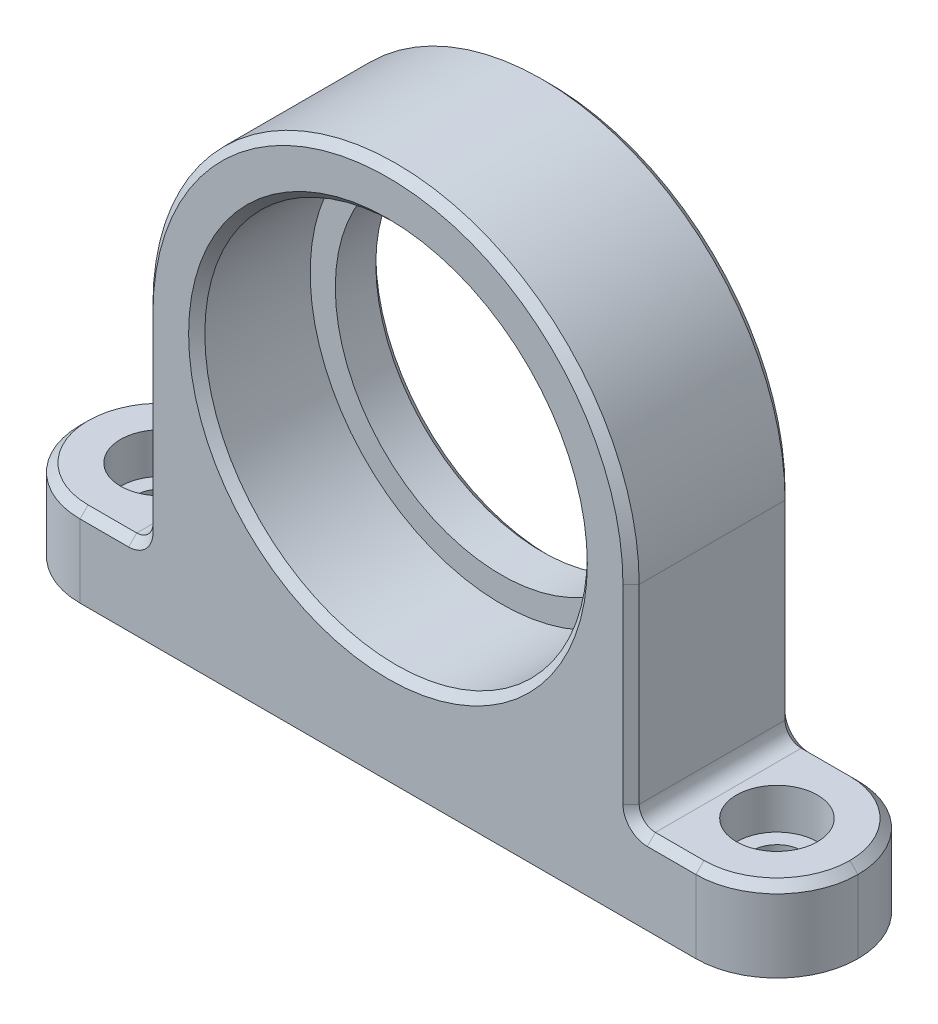
SolidWorks part; units mm, degrees
material "ABS"
ref_plane "前视基准面" through (0, 0, 0) normal (0, 0, 1) x (1, 0, 0)
ref_plane "上视基准面" through (0, 0, 0) normal (0, 1, 0) x (1, 0, 0)
ref_plane "右视基准面" through (0, 0, 0) normal (1, 0, 0) x (0, 0, -1)
sketch "草图1" plane through (0, 0, 0) normal (0, 1, 0) x (1, 0, 0)
  line L1 (-48, 10) -> (48, 10)
  line L2 (-48, 10) -> (-48, -10)
  line L3 (-48, -10) -> (48, -10)
  line L4 (48, 10) -> (48, -10)
  line L5 (-48, 10) -> (48, -10) construction
  line L6 (-48, -10) -> (48, 10) construction
  point P0 (0, 0)
extrude "凸台-拉伸1" add sketch "草图1" along normal blind 10 contours L2 L3 L4 L1
sketch "草图2" plane through (0, 10, 0) normal (0, 1, 0) x (1, 0, 0)
  line L0 (-48, 0) -> (-38, 0) construction
  line L1 (-48, 10) -> (-48, -10) construction
  line L2 (0, 0) -> (0, 10) construction
  line L3 (-48, 10) -> (48, 10) construction
  circle A0 centre (-38, 0) radius 5
  circle A1 centre (38, 0) radius 5
extrude "切除-拉伸1" cut sketch "草图2" against normal blind 5
fillet "圆角1" radius 10 4 edges at (48, 5, -10) (48, 5, 10) (-48, 5, 10) (-48, 5, -10)
sketch "草图3" plane through (0, 5, 0) normal (0, 1, 0) x (1, 0, 0)
  circle A0 centre (-38, 0) radius 3.1
  circle A1 centre (38, 0) radius 3.1
extrude "切除-拉伸2" cut sketch "草图3" against normal blind 5
chamfer "倒角1" distance 1 angle 45 2 edges at (38, 0, 3.1) (-38, 0, 3.1)
sketch "草图4" plane through (0, 10, 0) normal (0, 1, 0) x (1, 0, 0)
  line L0 (-38, 10) -> (38, 10) construction
  line L1 (-30, -10) -> (30, -10)
  line L2 (-30, -10) -> (-30, 10)
  line L3 (-30, 10) -> (30, 10)
  line L4 (30, -10) -> (30, 10)
  line L5 (-30, -10) -> (30, 10) construction
  line L6 (-30, 10) -> (30, -10) construction
  point P0 (0, 0)
extrude "凸台-拉伸2" add sketch "草图4" along normal blind 55.5
sketch "草图6" plane through (0, 0, 10) normal (0, 0, 1) x (1, 0, 0)
  line L0 (0, 0) -> (0, 65.5) construction
  line L1 (-30, 35.5) -> (30, 35.5) construction
  line L2 (-30, 65.5) -> (30, 65.5) construction
  line L3 (0, 65.5) -> (0, 35.5) construction
  circle A1 centre (0, 35.5) radius 23.6
  arc A2 (30, 35.5) -> (-30, 35.5) centre (0, 35.5) ccw
  dimension "D1" = 35.5
extrude "切除-拉伸3" cut sketch "草图6" against normal through all and the other way through all flip side to cut contours A2
extrude "切除-拉伸4" cut sketch "草图6<4>" against normal blind 14 contours A1
sketch "草图6<4>" plane through (0, 0, 10) normal (0, 0, 1) x (1, 0, 0) same geometry as "草图6"
sketch "草图7" plane through (0, 0, -4) normal (0, 0, 1) x (1, 0, 0)
  circle A0 centre (0, 35.5) radius 20.5
extrude "切除-拉伸5" cut sketch "草图7" against normal blind 10
fillet "圆角2" radius 2 2 edges at (30, 10, 0) (-30, 10, 0)
chamfer "倒角2" distance 1 angle 45 18 edges at (0, 65.5, -10) (30, 23.75, -10) (-30, 23.75, -10) (30.5858, 10.5858, -10) (-30.5858, 10.5858, -10) (35, 10, -10) (-35, 10, -10) (45.0711, 10, -7.0711) (-45.0711, 10, -7.0711) (45.0711, 10, 7.0711) (-45.0711, 10, 7.0711) (35, 10, 10) (-35, 10, 10) (30.5858, 10.5858, 10) (-30.5858, 10.5858, 10) (30, 23.75, 10) (-30, 23.75, 10) (0, 65.5, 10)
chamfer "倒角3" distance 1 angle 45 2 edges at (-20.5, 35.5, -10) (23.6, 35.5, 10)
